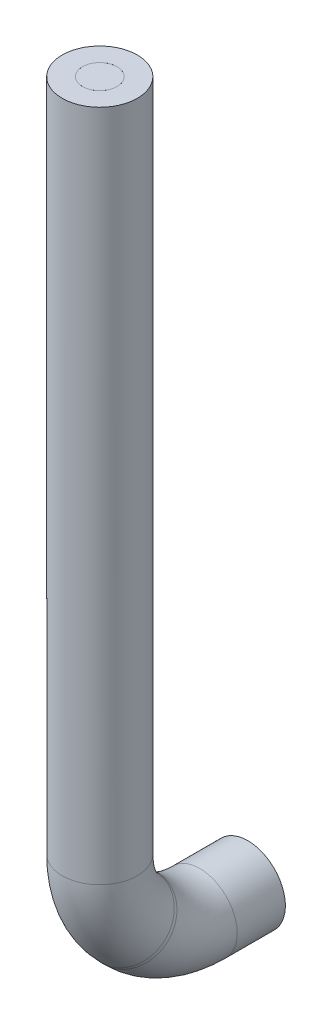
SolidWorks part; units mm, degrees
ref_plane "Спереди" through (0, 0, 0) normal (0, 0, 1) x (1, 0, 0)
ref_plane "Сверху" through (0, 0, 0) normal (0, 1, 0) x (1, 0, 0)
ref_plane "Справа" through (0, 0, 0) normal (1, 0, 0) x (0, 0, -1)
sketch "Эскиз1" plane through (0, 0, 0) normal (1, 0, 0) x (0, 0, -1)
  line L0 (0, 0) -> (-50000, 0) construction
  line L1 (0, 0) -> (0, 50000) construction
  line L2 (0, 17.5) -> (0, 2.2613)
  line L3 (0.6444, 0.7056) -> (0.7056, 0.6444)
  line L4 (2.2613, 0) -> (3.35, 0)
  arc A0 (0.7056, 0.6444) -> (2.2613, 0) centre (2.2613, 2.2) ccw
  arc A1 (0, 2.2613) -> (0.6444, 0.7056) centre (2.2, 2.2613) ccw
  point P11 (1.35, 0)
  point P14 (0, 1.35)
  dimension "D1" = 2.2
  dimension "D2" = 15.2387
  dimension "D3" = 45
  dimension "D4" = 3.35
  dimension "D5" = 2.2613
ref_plane "Плоскость1" through (0, 0, -3.35) normal (0, 0, 1) x (1, 0, 0)
sketch "Эскиз2" plane through (0, 0, -3.35) normal (0, 0, 1) x (1, 0, 0)
  circle A0 centre (0, 0) radius 0.39
  dimension "D1" = 0.78
sweep "По траектории1" add profiles "Эскиз2" path "Эскиз1"
sketch "Эскиз3" plane through (0, 0, -3.35) normal (0, 0, -1) x (-1, 0, 0)
  circle A0 centre (0, 0) radius 0.85
  circle A1 centre (0, 0) radius 0.39 construction
  circle A2 centre (0, 0) radius 0.39
  dimension "D1" = 1.7
sweep "По траектории2" add profiles "Эскиз3" path "Эскиз1<2>"
sketch "Эскиз1<2>" plane through (0, 0, 0) normal (1, 0, 0) x (0, 0, -1) same geometry as "Эскиз1"
